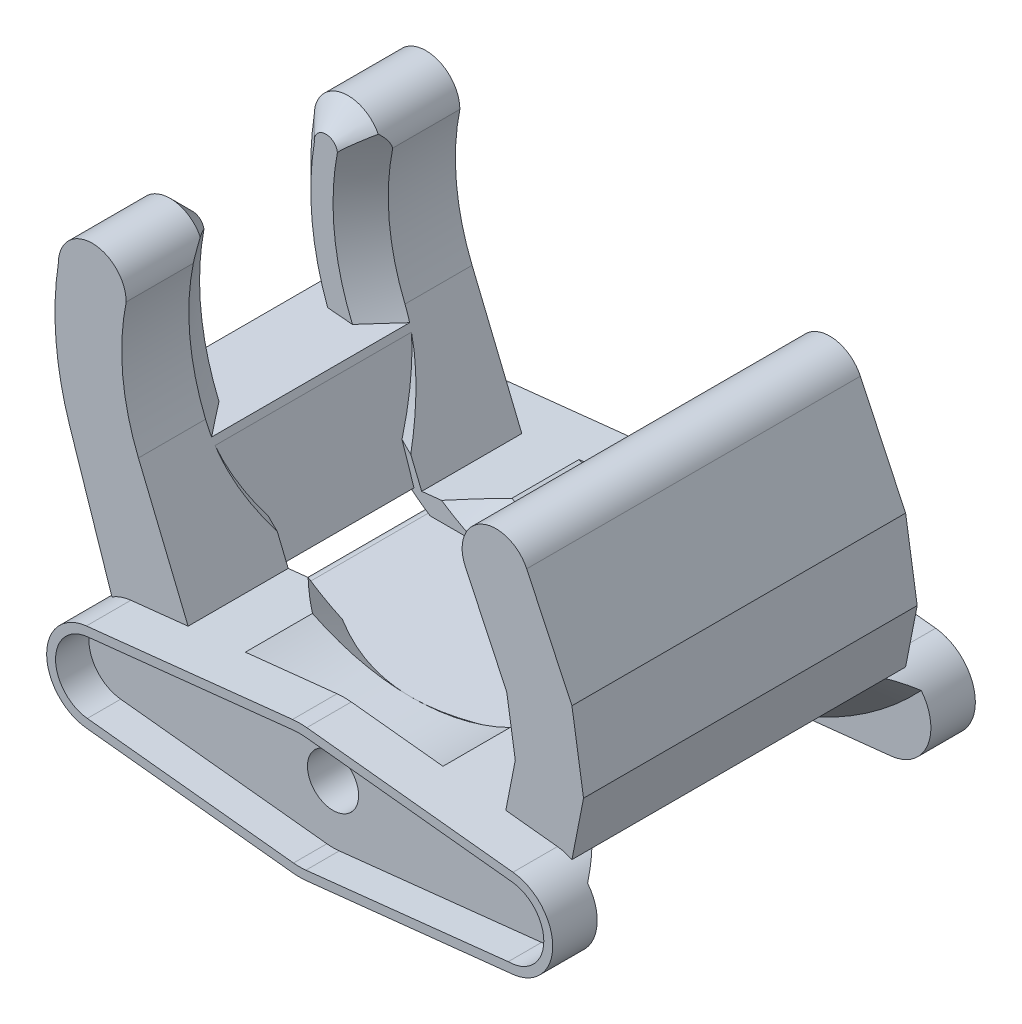
SolidWorks part; units mm, degrees
ref_plane "Front Plane" through (0, 0, 0) normal (0, 0, 1) x (1, 0, 0)
ref_plane "Top Plane" through (0, 0, 0) normal (0, 1, 0) x (1, 0, 0)
ref_plane "Right Plane" through (0, 0, 0) normal (1, 0, 0) x (0, 0, -1)
sketch "Sketch1" plane through (0, 0, 0) normal (0, 0, 1) x (1, 0, 0)
  line L1 (0, -12.7) -> (0, -20.32) construction
  arc A2 (-24.8887, 17.7709) -> (22.4603, 0.8386) centre (0, 12.7) ccw
  arc A3 (-32.6283, 17.7709) -> (29.7214, -1.686) centre (0, 12.7) ccw
  arc A7 (-24.8887, 17.7709) -> (-32.6283, 17.7709) centre (-28.7585, 17.7709) ccw
  arc A9 (29.7214, -1.686) -> (22.4603, 0.8386) centre (26.2382, 0) ccw
  point P11 (0, -12.7)
  point P13 (0, 0)
  point P15 (0, -20.32)
  dimension "D2" = 100
  dimension "D3" = 33.02
  dimension "D6" = 25.4
  dimension "D5" = 12.7
extrude "arm extrude" add sketch "Sketch1" along normal blind 38.1
sketch "Sketch2" plane through (0, 0, 38.1) normal (0, 0, 1) x (1, 0, 0)
  circle A1 centre (26.2382, 0) radius 0.5463
  arc A3 (29.7214, -1.686) -> (22.4603, 0.8386) centre (26.2382, 0) ccw construction
extrude "guide hole" cut sketch "Sketch2" against normal blind 0.508
ref_plane "Plane1" through (0, 0, 19.05) normal (0, 0, 1) x (1, 0, 0)
mirror "Mirror1" about plane through (0, 0, 19.05) normal (0, 0, 1) of "guide hole"
sketch "Sketch4" plane through (0, 0, 0) normal (1, 0, 0) x (0, 0, -1)
  line L1 (-26.67, 28.1064) -> (-11.43, 28.1064)
  line L2 (-26.67, 28.1064) -> (-26.67, -12.7)
  line L3 (-26.67, -12.7) -> (-11.43, -12.7)
  line L4 (-11.43, 28.1064) -> (-11.43, -12.7)
  line L6 (-38.1, -12.7) -> (0, -12.7) construction
  point P4 (-19.05, 28.1064)
  dimension "D1" = 15.24
extrude "mid cut" cut sketch "Sketch4" against normal through all and the other way through all contours L2 L3 L4 L1
chamfer "Chamfer1" distance 2.54 angle 56 2 edges at (13.1126, -9.0536, 26.67) (-19.6718, -3.368, 26.67) first distance on face at (19.2928, -6.4383, 26.67) first distance on face at (-22.4657, 1.6468, 26.67)
sketch "Sketch5" plane through (0, 0, 38.1) normal (0, 0, 1) x (1, 0, 0)
  line L0 (0, -12.7) -> (0, -20.32) construction
  line L1 (-24.3544, -11.459) -> (-0.8128, -8.9335)
  line L2 (0.8128, -8.9335) -> (24.3544, -11.459)
  line L3 (24.3544, -21.561) -> (0.8128, -24.0865)
  line L4 (-24.3544, -21.561) -> (-0.8128, -24.0865)
  line L5 (-23.8125, -16.51) -> (23.8125, -16.51) construction
  arc A0 (-32.6283, 17.7709) -> (29.7214, -1.686) centre (0, 12.7) ccw construction
  arc A1 (-0.8128, -24.0865) -> (0.8128, -24.0865) centre (0, -16.51) ccw
  arc A2 (-24.3544, -11.459) -> (-24.3544, -21.561) centre (-23.8125, -16.51) ccw
  arc A3 (24.3544, -21.561) -> (24.3544, -11.459) centre (23.8125, -16.51) ccw
  arc A4 (0.8128, -8.9335) -> (-0.8128, -8.9335) centre (0, -16.51) ccw
  point P0 (0, -12.7)
  point P1 (0, -20.32)
  point P22 (0, -16.51)
  dimension "D3" = 15.24
  dimension "D4" = 10.16
  dimension "D1" = 47.625
extrude "servo horn base" add sketch "Sketch5" along normal blind 1.27
sketch "Sketch6" plane through (0, 0, 39.37) normal (0, 0, 1) x (1, 0, 0)
  line L0 (-23.8125, -16.51) -> (23.8125, -16.51) construction
  line L1 (-24.246, -12.4692) -> (-0.7044, -9.9437)
  line L2 (0.7044, -9.9437) -> (24.246, -12.4692)
  line L3 (23.8125, -20.574) -> (0.711, -23.0756)
  line L4 (-24.246, -20.5508) -> (-0.7044, -23.0763)
  line L30 (24.3544, -11.459) -> (0.8128, -8.9335)
  line L31 (0.8128, -24.0865) -> (24.3544, -21.561)
  line L32 (-24.3544, -21.561) -> (-0.8128, -24.0865)
  line L33 (-0.8128, -8.9335) -> (-24.3544, -11.459)
  line L34 (24.3544, -11.459) -> (0.8128, -8.9335)
  line L35 (0.8128, -24.0865) -> (24.3544, -21.561)
  line L36 (-24.3544, -21.561) -> (-0.8128, -24.0865)
  line L37 (-0.8128, -8.9335) -> (-24.3544, -11.459)
  arc A0 (0.8128, -8.9335) -> (-0.8128, -8.9335) centre (0, -16.51) ccw construction
  arc A1 (-0.7044, -23.0763) -> (0.711, -23.0756) centre (0, -16.51) ccw
  arc A2 (-24.246, -12.4692) -> (-24.246, -20.5508) centre (-23.8125, -16.51) ccw
  arc A3 (23.8125, -20.574) -> (24.246, -12.4692) centre (23.8125, -16.51) ccw
  arc A4 (24.3544, -21.561) -> (24.3544, -11.459) centre (23.8125, -16.51) ccw construction
  arc A5 (0.7044, -9.9437) -> (-0.7044, -9.9437) centre (0, -16.51) ccw
  arc A25 (24.3544, -21.561) -> (24.3544, -11.459) centre (23.8125, -16.51) ccw
  arc A26 (0.8128, -8.9335) -> (-0.8128, -8.9335) centre (0, -16.51) ccw
  arc A27 (-0.8128, -24.0865) -> (0.8128, -24.0865) centre (0, -16.51) ccw
  arc A28 (-24.3544, -11.459) -> (-24.3544, -21.561) centre (-23.8125, -16.51) ccw
  arc A29 (24.3544, -21.561) -> (24.3544, -11.459) centre (23.8125, -16.51) ccw
  arc A30 (0.8128, -8.9335) -> (-0.8128, -8.9335) centre (0, -16.51) ccw
  arc A31 (-0.8128, -24.0865) -> (0.8128, -24.0865) centre (0, -16.51) ccw
  arc A32 (-24.3544, -11.459) -> (-24.3544, -21.561) centre (-23.8125, -16.51) ccw
  point P0 (0, -8.89)
  dimension "D1" = 8.128
  dimension "D2" = 13.208
  dimension "D3" = 0
extrude "servo horn extrude" add sketch "Sketch6" along normal blind 3.81
fillet "Fillet1" radius 1.27 2 edges at (-21.0988, -12.7, 19.05) (21.0988, -12.7, 19.05)
chamfer "Chamfer2" distance 5.08 angle 45 1 edges at (0, -20.32, 38.1)
sketch "Sketch7" plane through (0, 0, 39.37) normal (0, 0, 1) x (1, 0, 0)
  circle A0 centre (0, -16.51) radius 2.921
  arc A1 (0.7044, -9.9437) -> (-0.7044, -9.9437) centre (0, -16.51) ccw construction
  dimension "D1" = 5.842
extrude "screwdriver hole" cut sketch "Sketch7" against normal through all
sketch "Sketch8" plane through (0, 0, 0) normal (0, 0, -1) x (-1, 0, 0)
  line L1 (-43.3229, 32.8392) -> (42.3138, 32.8392)
  line L2 (-43.3229, 32.8392) -> (-43.3229, -33.1665)
  line L3 (-43.3229, -33.1665) -> (42.3138, -33.1665)
  line L4 (42.3138, 32.8392) -> (42.3138, -33.1665)
ref_plane "Plane2" through (0, 0, 19.05) normal (0, 0, -1) x (-1, 0, 0)
extrude "Cut-Extrude1" cut sketch "Sketch8" against normal up to surface (19.05 mm away) contours L1 L4 L3 L2 up to plane "Plane2"
mirror "Mirror2" about plane through (0, 0, 19.05) normal (0, 0, -1) of bodies 108
chamfer "Chamfer3" distance 2.54 angle 45 4 edges at (-30.1293, -0.811, 11.43) (-30.6149, 21.1664, 11.43) (-30.6149, 21.1664, 26.67) (-30.1293, -0.811, 26.67)
chamfer "Chamfer4" distance 2.54 angle 45 4 edges at (24.7366, -9.1729, 26.67) (25.684, 3.8299, 26.67) (24.7366, -9.1729, 11.43) (25.684, 3.8299, 11.43)
sketch "Sketch9" plane through (0, 0, 38.1) normal (0, 0, 1) x (1, 0, 0)
  line L0 (-31.3331, 2.281) -> (-26.515, -12.2085)
  line L1 (-31.3331, 2.281) -> (-22.8184, 1.543)
  line L2 (-22.8184, 1.543) -> (-18.6968, -10.852)
  line L3 (-11.2825, -10.0566) -> (-22.6984, -11.2813) construction
  line L6 (-0.8128, -8.9335) -> (-24.3544, -11.459)
  line L7 (-18.6968, -10.852) -> (-24.3544, -11.459)
  arc A0 (-32.6283, 17.7709) -> (-22.6984, -11.2813) centre (0, 12.7) ccw construction
  arc A1 (-24.3544, -11.459) -> (-24.3544, -21.561) centre (-23.8125, -16.51) ccw construction
  arc A2 (-24.8887, 17.7709) -> (-11.2825, -10.0566) centre (0, 12.7) ccw construction
  arc A6 (-24.3544, -11.459) -> (-24.3544, -21.561) centre (-23.8125, -16.51) ccw
  arc A7 (-24.3544, -11.459) -> (-26.515, -12.2085) centre (-23.8125, -16.51) ccw
  point P5 (-31.3331, 2.281)
  dimension "D1" = 0
extrude "Boss-Extrude1" add sketch "Sketch9" against normal up to surface (38.1 mm away) up to face at (-24.9532, 3.6338, 0)
sketch "Sketch10" plane through (0, 0, 38.1) normal (0, 0, 1) x (1, 0, 0)
  line L0 (-23.4919, 3.0414) -> (-17.8184, -10.7578)
  line L1 (-11.2825, -10.0566) -> (-24.3544, -11.459) construction
  line L2 (-17.8184, -10.7578) -> (-8.9963, -9.8114)
  line L3 (-0.8128, -8.9335) -> (-24.3544, -11.459) construction
  line L4 (-8.9963, -9.8114) -> (-23.4919, 3.0414)
  arc A0 (-24.8887, 17.7709) -> (-11.2825, -10.0566) centre (0, 12.7) ccw construction
extrude "Cut-Extrude2" cut sketch "Sketch10" against normal through all
sketch "Sketch13" plane through (0, 0, 38.1) normal (0, 0, 1) x (1, 0, 0)
  line L0 (10.1495, -9.9351) -> (36.0514, -12.7138)
  line L1 (24.3544, -11.459) -> (0.8128, -8.9335) construction
  line L2 (36.0514, -12.7138) -> (36.6501, 7.2665)
  line L3 (36.6501, 7.2665) -> (8.1468, 13.8399)
  line L4 (8.1468, 13.8399) -> (10.1495, -9.9351)
extrude "Cut-Extrude4" cut sketch "Sketch13" against normal through all
sketch "Sketch14" plane through (0, 0, 38.1) normal (0, 0, 1) x (1, 0, 0)
  line L0 (26.0075, -11.9287) -> (27.3321, -5.1912)
  line L1 (24.3544, -11.459) -> (0.8128, -8.9335) construction
  line L2 (27.3321, -5.1912) -> (26.0075, 3.2904)
  line L3 (18.5588, 0.9403) -> (19.5385, -5.3324)
  line L4 (19.5385, -5.3324) -> (18.4294, -10.9735)
  line L5 (18.4294, -10.9735) -> (26.0075, -11.9287)
  line L6 (18.5588, 0.9403) -> (13.8413, 10.9476)
  line L7 (26.0075, 3.2904) -> (20.842, 14.2478)
  arc A1 (20.842, 14.2478) -> (13.8413, 10.9476) centre (17.3416, 12.5977) ccw
  arc A3 (-24.8887, 17.7709) -> (-32.6283, 17.7709) centre (-28.7585, 17.7709) ccw construction
  arc A4 (24.3544, -21.561) -> (24.3544, -11.459) centre (23.8125, -16.51) ccw construction
  point P8 (26.0075, 3.2904)
  point P15 (0, 0)
  point P17 (18.3295, -2.6038)
  point P18 (0, 0)
  point P19 (26.0075, -11.9287)
  dimension "D1" = 7.62
  dimension "D3" = 95
  dimension "D4" = 160
extrude "Boss-Extrude3" add sketch "Sketch14" against normal up to surface (38.1 mm away) separate body
